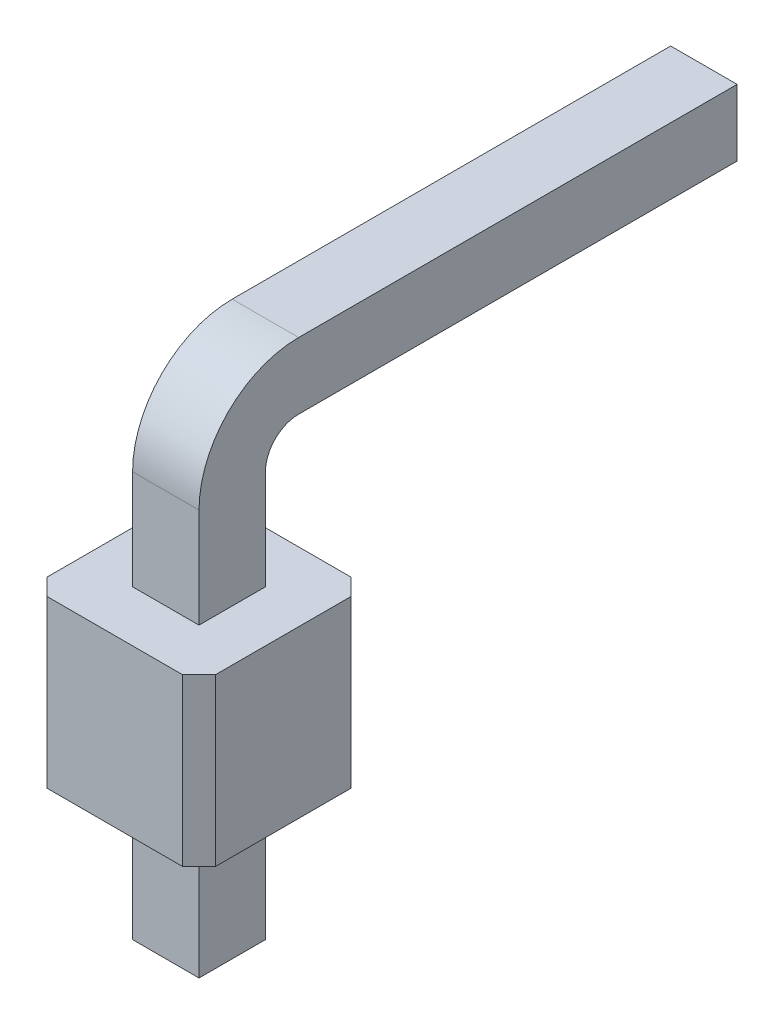
SolidWorks part; units mm, degrees
ref_plane "Front Plane" through (0, 0, 0) normal (0, 0, 1) x (1, 0, 0)
ref_plane "Top Plane" through (0, 0, 0) normal (0, 1, 0) x (1, 0, 0)
ref_plane "Right Plane" through (0, 0, 0) normal (1, 0, 0) x (0, 0, -1)
ref_plane "Plane1" through (0, 0, 0) normal (0, 1, 0) x (-1, 0, 0)
sketch "Sketch1" plane through (0, 0, 0) normal (0, 1, 0) x (-1, 0, 0)
  line L0 (-1.02, 1.27) -> (1.02, 1.27)
  line L1 (1.27, 1.02) -> (1.27, -1.02)
  line L2 (1.02, -1.27) -> (-1.02, -1.27)
  line L3 (-1.27, -1.02) -> (-1.27, 1.02)
  line L4 (1.02, 1.27) -> (1.27, 1.02)
  line L5 (-1.02, 1.27) -> (-1.27, 1.02)
  line L6 (1.27, -1.02) -> (1.02, -1.27)
  line L7 (-1.02, -1.27) -> (-1.27, -1.02)
  dimension "D1" = 1.27
  dimension "D2" = 1.27
  dimension "D4" = 2.54
  dimension "D5" = 135
  dimension "D6" = 0.25
extrude "Boss-Extrude1" add sketch "Sketch1" along normal blind 2.5
ref_plane "Plane2" through (0, 0, 0) normal (1, 0, 0) x (0, 0, -1)
sketch "Sketch2" plane through (0, 0, 0) normal (1, 0, 0) x (0, 0, -1)
  line L0 (0, 0) -> (0, 4)
  line L1 (1, 5) -> (8, 5)
  line L2 (0, 0) -> (0, -2.5)
  arc A0 (1, 5) -> (0, 4) centre (1, 4) ccw
  dimension "D3" = 1
  dimension "D1" = 2.5
  dimension "D2" = 4
  dimension "D4" = 8
extrude "Extrude-Thin1" add sketch "Sketch2" along normal blind 0.5 and the other way blind 0.5 thin thin type mid plane wall 1
chamfer "Chamfer1" distance 0.4 angle 45 8 edges at (-0.5, 5, -8) (0, 4.5, -8) (0.5, 5, -8) (0, 5.5, -8) (0, -2.5, -0.5) (-0.5, -2.5, 0) (0, -2.5, 0.5) (0.5, -2.5, 0)
ref_axis "Axis1" through (0, 5.9, 0) along (0, -1, 0)
